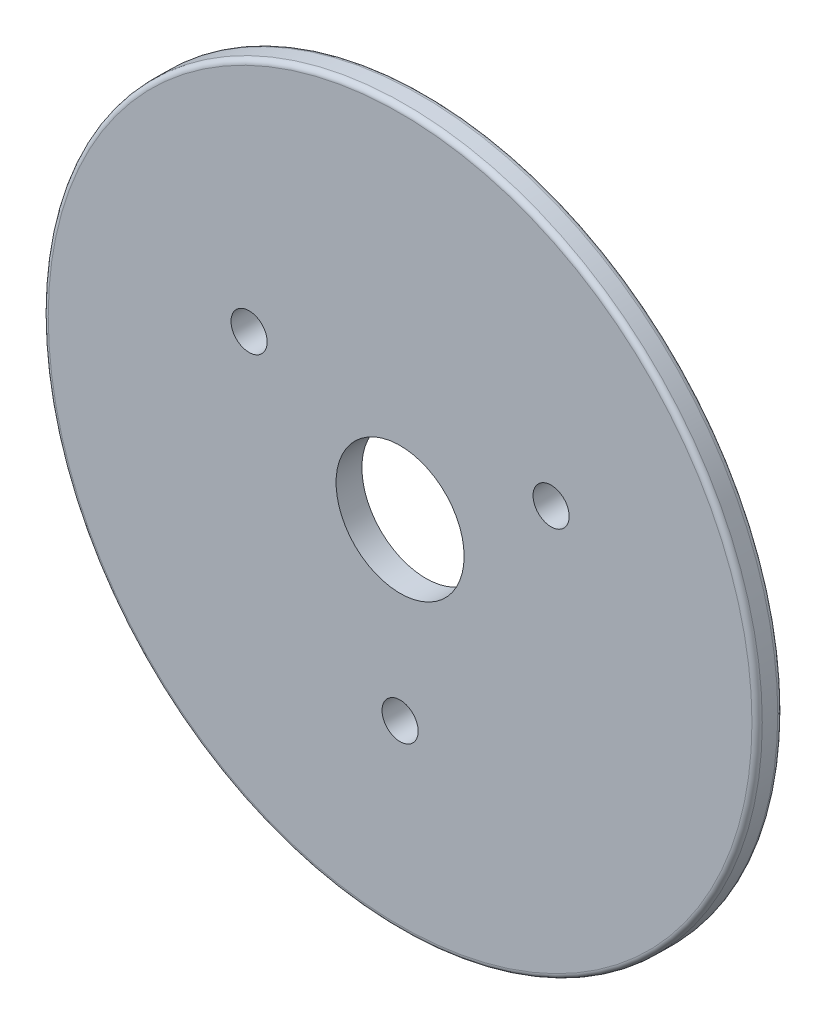
SolidWorks part; units mm, degrees
ref_plane "Front Plane" through (0, 0, 0) normal (0, 0, 1) x (1, 0, 0)
ref_plane "Top Plane" through (0, 0, 0) normal (0, 1, 0) x (1, 0, 0)
ref_plane "Right Plane" through (0, 0, 0) normal (1, 0, 0) x (0, 0, -1)
sketch "Sketch1" plane through (0, 0, 0) normal (0, 1, 0) x (1, 0, 0)
  line L0 (0, 36.1296) -> (0, -19.4741) construction
sketch "Sketch7" plane through (0, 0, 0) normal (0, 0, 1) x (1, 0, 0)
  line L0 (0, 0) -> (0, 28.5291) construction
  line L1 (-2.325, 29.4841) -> (-2.9401, 31.1741) construction
  line L2 (-2.325, 29.4841) -> (-1.6298, 27.5741) construction
  line L3 (-1.6298, 27.5741) -> (1.6298, 27.5741) construction
  line L4 (1.6298, 27.5741) -> (2.325, 29.4841) construction
  line L5 (2.325, 29.4841) -> (-2.325, 29.4841) construction
  line L6 (0, 27.5741) -> (0, 29.4841) construction
  line L7 (2.325, 29.4841) -> (2.9401, 31.1741) construction
  line L8 (-2.9401, 31.1741) -> (2.9401, 31.1741) construction
  line L9 (0, 0) -> (8.816, 27.1328) construction
  line L10 (8.816, 27.1328) -> (9.1394, 28.1281) construction
  line L11 (0, 29.4841) -> (0, 29.5757) construction
  line L12 (0, 29.5757) -> (0, 31.3125) construction
  line L13 (0, 30.4441) -> (9.4077, 28.954) construction
  line L14 (9.1394, 28.1281) -> (9.6761, 29.7799) construction
  circle A1 centre (0, 0) radius 28.5291 construction
  circle A2 centre (-1.2727, 28.0841) radius 0.51 construction
  circle A3 centre (1.2727, 28.0841) radius 0.51 construction
  circle A4 centre (0, 0) radius 29.5757
  circle A5 centre (0, 0) radius 31.3125 construction
  dimension "D3" = 40
  dimension "D6" = 1.02
  dimension "D1" = 3.6
  dimension "D2" = 18
  dimension "D7" = 9.525
  dimension "D4" = 1.91
  dimension "D5" = 4.65
extrude "Boss-Extrude1" add sketch "Sketch7" along normal blind 7.25 and the other way blind 7.25 contours A4 region at (0, 0, 0)
sketch "Sketch14" plane through (0, 0, 0) normal (1, 0, 0) x (0, 0, -1)
  line L0 (-18, 0) -> (-18, 10)
  line L1 (-18, 0) -> (0, 0)
  line L2 (0, 0) -> (0, 19)
  line L3 (0, 19) -> (-7.25, 19)
  line L4 (-7.25, 19) -> (-18, 10)
  line L5 (-7.25, 29.5757) -> (-7.25, -29.5757) construction
  line L6 (-18, 6.7395) -> (-3.3555, 19) construction
  arc A0 (-7.25, 19) -> (-18, 10) centre (-18.1316, 21.0773) cw
  dimension "D1" = 10
  dimension "D2" = 19
  dimension "D3" = 18
  dimension "D4" = 2.5
revolve "Revolve1" add sketch "Sketch14" angle 360 about L0 region at (0, 7.5733, 7.5341) region at (0, 9.2725, 16.1663) region at (0, 17.2765, 6.6188)
sketch "Sketch9" plane through (0, 0, 0) normal (0, 0, 1) x (1, 0, 0)
  line L0 (2, 0) -> (-2, 0) construction
  line L1 (-2, 0) -> (-2, 7.5) construction
  line L2 (-2, 7.5) -> (2, 7.5) construction
  line L3 (2, 7.5) -> (2, 0) construction
  circle A0 centre (0, 0) radius 6 construction
  dimension "D1" = 12
  dimension "D2" = 4
  dimension "D3" = 7.5
sketch "Sketch10" plane through (0, 0, 0) normal (0, 0, 1) x (1, 0, 0)
  line L0 (2, 0) -> (-2, 0) construction
  line L1 (-2.2, 7.7) -> (2.2, 7.7)
  line L2 (-2.2, 7.7) -> (-2.2, 0)
  line L3 (-2.2, 0) -> (2.2, 0)
  line L4 (2.2, 7.7) -> (2.2, 0)
  line L5 (-2, 7.5) -> (2, 7.5) construction
  line L6 (2, 7.5) -> (2, 0) construction
  circle A0 centre (0, 0) radius 6.2
  circle A1 centre (0, 0) radius 6 construction
  dimension "D1" = 0.2
  dimension "D2" = 0.2
  dimension "D3" = 0.2
extrude "Cut-Extrude3" cut sketch "Sketch10" against normal through all both and the other way through all contours A0 L4 L1 L2 | L2 A0 L4 L3 | L4 A0 L2 L3 region at (0, 6.8793, 0) region at (0, 3.0348, 0) region at (0, -0.8613, 0)
sketch "Sketch11" [suppressed] plane through (0, 0, 0) normal (0, 1, 0) x (1, 0, 0)
  line L0 (29.5757, 7.25) -> (-29.5757, 7.25) construction
  line L1 (11, 7.25) -> (17.5, 7.25)
  line L2 (11, 7.25) -> (11, 4.75)
  line L3 (11, 4.75) -> (17.5, 4.75)
  line L4 (17.5, 7.25) -> (17.5, 4.75)
  line L5 (-29.5757, -7.25) -> (29.5757, -7.25) construction
  line L6 (11, -7.25) -> (17.5, -7.25)
  line L7 (11, -7.25) -> (11, -4.75)
  line L8 (11, -4.75) -> (17.5, -4.75)
  line L9 (17.5, -7.25) -> (17.5, -4.75)
  line L11 (11, 4.75) -> (11, -4.75) construction
  line L12 (17.5, -4.75) -> (17.5, 4.75) construction
  line L13 (6.2, 7.25) -> (-6.2, 7.25) construction
  line L14 (0, 7.25) -> (22.5, 7.25)
  line L15 (0, 7.25) -> (0, -7.25)
  line L16 (0, -7.25) -> (22.5, -7.25)
  line L17 (22.5, 7.25) -> (22.5, -7.25)
  line L18 (-6.2, -7.25) -> (6.2, -7.25) construction
  line L19 (6, 7.25) -> (6, -7.25) construction
  dimension "D1" = 22.5
  dimension "D2" = 6
  dimension "D3" = 5
  dimension "D4" = 5
  dimension "D5" = 2.5
sketch "Sketch15" plane through (0, 0, -7.25) normal (0, 0, -1) x (-1, 0, 0)
  circle A0 centre (0, 0) radius 8.0081
  circle A1 centre (0, 0) radius 2.25
  dimension "D1" = 4.5
extrude "Boss-Extrude2" add sketch "Sketch15" against normal blind 5.5
sketch "Sketch16" plane through (0, 0, -7.25) normal (0, 0, -1) x (-1, 0, 0)
  circle A0 centre (0, 0) radius 5
  dimension "D1" = 10
extrude "Cut-Extrude4" cut sketch "Sketch16" against normal blind 3
sketch "Sketch17" plane through (0, 0, -7.25) normal (0, 0, -1) x (-1, 0, 0)
  circle A0 centre (0, 0) radius 29.5757
  circle A1 centre (0, 0) radius 29.5757 construction
  circle A2 centre (0, 0) radius 5
  circle A3 centre (0, 0) radius 5 construction
extrude "Boss-Extrude3" add sketch "Sketch17" along normal blind 7.5
sketch "Sketch8" plane through (0, 0, 0) normal (0, 0, 1) x (1, 0, 0)
  line L6 (-1.6298, 27.5741) -> (-2.3583, 29.5757)
  line L7 (-2.3583, 29.5757) -> (2.3583, 29.5757)
  line L8 (2.3583, 29.5757) -> (1.6298, 27.5741)
  line L9 (1.6298, 27.5741) -> (-1.6298, 27.5741)
  line L10 (-2.325, 29.4841) -> (-1.6298, 27.5741) construction
  line L11 (1.6298, 27.5741) -> (2.325, 29.4841) construction
  line L12 (6.9708, 26.7282) -> (6.8965, 28.8569)
  line L13 (6.8965, 28.8569) -> (11.3823, 27.3994)
  line L14 (11.3823, 27.3994) -> (10.0709, 25.7209)
  line L15 (10.0709, 25.7209) -> (6.9708, 26.7282)
  line L16 (14.8891, 23.2659) -> (15.4762, 25.3134)
  line L17 (15.4762, 25.3134) -> (19.292, 22.541)
  line L18 (19.292, 22.541) -> (17.5262, 21.35)
  line L19 (17.5262, 21.35) -> (14.8891, 23.2659)
  line L20 (21.35, 17.5262) -> (22.541, 19.292)
  line L21 (22.541, 19.292) -> (25.3134, 15.4762)
  line L22 (25.3134, 15.4762) -> (23.2659, 14.8891)
  line L23 (23.2659, 14.8891) -> (21.35, 17.5262)
  line L24 (25.7209, 10.0709) -> (27.3994, 11.3823)
  line L25 (27.3994, 11.3823) -> (28.8569, 6.8965)
  line L26 (28.8569, 6.8965) -> (26.7282, 6.9708)
  line L27 (26.7282, 6.9708) -> (25.7209, 10.0709)
  line L28 (27.5741, 1.6298) -> (29.5757, 2.3583)
  line L29 (29.5757, 2.3583) -> (29.5757, -2.3583)
  line L30 (29.5757, -2.3583) -> (27.5741, -1.6298)
  line L31 (27.5741, -1.6298) -> (27.5741, 1.6298)
  line L32 (26.7282, -6.9708) -> (28.8569, -6.8965)
  line L33 (28.8569, -6.8965) -> (27.3994, -11.3823)
  line L34 (27.3994, -11.3823) -> (25.7209, -10.0709)
  line L35 (25.7209, -10.0709) -> (26.7282, -6.9708)
  line L36 (23.2659, -14.8891) -> (25.3134, -15.4762)
  line L37 (25.3134, -15.4762) -> (22.541, -19.292)
  line L38 (22.541, -19.292) -> (21.35, -17.5262)
  line L39 (21.35, -17.5262) -> (23.2659, -14.8891)
  line L40 (17.5262, -21.35) -> (19.292, -22.541)
  line L41 (19.292, -22.541) -> (15.4762, -25.3134)
  line L42 (15.4762, -25.3134) -> (14.8891, -23.2659)
  line L43 (14.8891, -23.2659) -> (17.5262, -21.35)
  line L44 (10.0709, -25.7209) -> (11.3823, -27.3994)
  line L45 (11.3823, -27.3994) -> (6.8965, -28.8569)
  line L46 (6.8965, -28.8569) -> (6.9708, -26.7282)
  line L47 (6.9708, -26.7282) -> (10.0709, -25.7209)
  line L48 (1.6298, -27.5741) -> (2.3583, -29.5757)
  line L49 (2.3583, -29.5757) -> (-2.3583, -29.5757)
  line L50 (-2.3583, -29.5757) -> (-1.6298, -27.5741)
  line L51 (-1.6298, -27.5741) -> (1.6298, -27.5741)
  line L52 (-6.9708, -26.7282) -> (-6.8965, -28.8569)
  line L53 (-6.8965, -28.8569) -> (-11.3823, -27.3994)
  line L54 (-11.3823, -27.3994) -> (-10.0709, -25.7209)
  line L55 (-10.0709, -25.7209) -> (-6.9708, -26.7282)
  line L56 (-14.8891, -23.2659) -> (-15.4762, -25.3134)
  line L57 (-15.4762, -25.3134) -> (-19.292, -22.541)
  line L58 (-19.292, -22.541) -> (-17.5262, -21.35)
  line L59 (-17.5262, -21.35) -> (-14.8891, -23.2659)
  line L60 (-21.35, -17.5262) -> (-22.541, -19.292)
  line L61 (-22.541, -19.292) -> (-25.3134, -15.4762)
  line L62 (-25.3134, -15.4762) -> (-23.2659, -14.8891)
  line L63 (-23.2659, -14.8891) -> (-21.35, -17.5262)
  line L64 (-25.7209, -10.0709) -> (-27.3994, -11.3823)
  line L65 (-27.3994, -11.3823) -> (-28.8569, -6.8965)
  line L66 (-28.8569, -6.8965) -> (-26.7282, -6.9708)
  line L67 (-26.7282, -6.9708) -> (-25.7209, -10.0709)
  line L68 (-27.5741, -1.6298) -> (-29.5757, -2.3583)
  line L69 (-29.5757, -2.3583) -> (-29.5757, 2.3583)
  line L70 (-29.5757, 2.3583) -> (-27.5741, 1.6298)
  line L71 (-27.5741, 1.6298) -> (-27.5741, -1.6298)
  line L72 (-26.7282, 6.9708) -> (-28.8569, 6.8965)
  line L73 (-28.8569, 6.8965) -> (-27.3994, 11.3823)
  line L74 (-27.3994, 11.3823) -> (-25.7209, 10.0709)
  line L75 (-25.7209, 10.0709) -> (-26.7282, 6.9708)
  line L76 (-23.2659, 14.8891) -> (-25.3134, 15.4762)
  line L77 (-25.3134, 15.4762) -> (-22.541, 19.292)
  line L78 (-22.541, 19.292) -> (-21.35, 17.5262)
  line L79 (-21.35, 17.5262) -> (-23.2659, 14.8891)
  line L80 (-17.5262, 21.35) -> (-19.292, 22.541)
  line L81 (-19.292, 22.541) -> (-15.4762, 25.3134)
  line L82 (-15.4762, 25.3134) -> (-14.8891, 23.2659)
  line L83 (-14.8891, 23.2659) -> (-17.5262, 21.35)
  line L84 (-10.0709, 25.7209) -> (-11.3823, 27.3994)
  line L85 (-11.3823, 27.3994) -> (-6.8965, 28.8569)
  line L86 (-6.8965, 28.8569) -> (-6.9708, 26.7282)
  line L87 (-6.9708, 26.7282) -> (-10.0709, 25.7209)
  circle A0 centre (0, 0) radius 29.5757 construction
  point P119 (0, 0)
  dimension "D1" = 20
extrude "Cut-Extrude2" cut sketch "Sketch8" against normal through all both and the other way through all
fillet "Fillet2" radius 0.51 80 edges at (-28.7595, -6.8999, -3.75) (-27.3226, -11.3223, -3.75) (-25.2198, -15.4494, -3.75) (-22.4866, -19.2113, -3.75) (-19.2113, -22.4866, -3.75) (-15.4494, -25.2198, -3.75) (-11.3223, -27.3226, -3.75) (-6.8999, -28.7595, -3.75) (-2.325, -29.4841, -3.75) (2.325, -29.4841, -3.75) (6.8999, -28.7595, -3.75) (11.3223, -27.3226, -3.75) (15.4494, -25.2198, -3.75) (19.2113, -22.4866, -3.75) (22.4866, -19.2113, -3.75) (25.2198, -15.4494, -3.75) (27.3226, -11.3223, -3.75) (28.7595, -6.8999, -3.75) (29.4841, -2.325, -3.75) (29.4841, 2.325, -3.75) (28.7595, 6.8999, -3.75) (27.3226, 11.3223, -3.75) (25.2198, 15.4494, -3.75) (22.4866, 19.2113, -3.75) (19.2113, 22.4866, -3.75) (15.4494, 25.2198, -3.75) (11.3223, 27.3226, -3.75) (6.8999, 28.7595, -3.75) (2.325, 29.4841, -3.75) (-26.7282, -6.9708, -3.75) (-25.7209, -10.0709, -3.75) (-23.2659, -14.8891, -3.75) (-21.35, -17.5262, -3.75) (-17.5262, -21.35, -3.75) (-14.8891, -23.2659, -3.75) (-10.0709, -25.7209, -3.75) (-6.9708, -26.7282, -3.75) (-1.6298, -27.5741, -3.75) (1.6298, -27.5741, -3.75) (6.9708, -26.7282, -3.75) (10.0709, -25.7209, -3.75) (14.8891, -23.2659, -3.75) (17.5262, -21.35, -3.75) (21.35, -17.5262, -3.75) (23.2659, -14.8891, -3.75) (25.7209, -10.0709, -3.75) (26.7282, -6.9708, -3.75) (27.5741, -1.6298, -3.75) (27.5741, 1.6298, -3.75) (26.7282, 6.9708, -3.75) (25.7209, 10.0709, -3.75) (23.2659, 14.8891, -3.75) (21.35, 17.5262, -3.75) (17.5262, 21.35, -3.75) (14.8891, 23.2659, -3.75) (10.0709, 25.7209, -3.75) (6.9708, 26.7282, -3.75) (1.6298, 27.5741, -3.75) (-1.6298, 27.5741, -3.75) (-2.325, 29.4841, -3.75) (-6.8999, 28.7595, -3.75) (-6.9708, 26.7282, -3.75) (-10.0709, 25.7209, -3.75) (-11.3223, 27.3226, -3.75) (-15.4494, 25.2198, -3.75) (-14.8891, 23.2659, -3.75) (-17.5262, 21.35, -3.75) (-19.2113, 22.4866, -3.75) (-22.4866, 19.2113, -3.75) (-21.35, 17.5262, -3.75) (-23.2659, 14.8891, -3.75) (-25.2198, 15.4494, -3.75) (-27.3226, 11.3223, -3.75) (-25.7209, 10.0709, -3.75) (-26.7282, 6.9708, -3.75) (-28.7595, 6.8999, -3.75) (-29.4841, 2.325, -3.75) (-27.5741, 1.6298, -3.75) (-27.5741, -1.6298, -3.75) (-29.4841, -2.325, -3.75)
sketch "Sketch18" plane through (0, 0, -14.75) normal (0, 0, -1) x (-1, 0, 0)
  circle A0 centre (0, 0) radius 5
  circle A1 centre (0, 0) radius 34.5757
  circle A2 centre (0, 0) radius 29.5757
  circle A3 centre (0, 0) radius 5 construction
  circle A4 centre (0, 0) radius 29.5757 construction
  dimension "D1" = 5
extrude "Boss-Extrude4" add sketch "Sketch18" along normal blind 2.5 contours A1 A2 | A2 A0 region at (33.5977, 0, -14.75) region at (28.7391, 0, -14.75)
sketch "Sketch19" plane through (0, 0, 7.25) normal (0, 0, 1) x (1, 0, 0)
  circle A0 centre (0, 0) radius 19
  circle A1 centre (0, 0) radius 34.5757
  circle A2 centre (0, 0) radius 34.5757 construction
  circle A3 centre (0, 0) radius 19 construction
extrude "Boss-Extrude5" add sketch "Sketch19" against normal blind 2.5
sketch "Sketch20" plane through (0, 0, 18) normal (0, 0, 1) x (1, 0, 0)
  line L0 (-2.2, 5.7966) -> (-2.2, 7.7)
  line L1 (-2.2, 7.7) -> (2.2, 7.7)
  line L2 (-2.2, 7.7) -> (2.2, 7.7) construction
  line L3 (2.2, 7.7) -> (2.2, 5.7966)
  circle A0 centre (0, 0) radius 6.2
  arc A1 (-2.2, 5.7966) -> (2.2, 5.7966) centre (0, 0) ccw construction
  arc M2 (2.2, 5.7966) -> (-2.2, 5.7966) centre (0, 0) cw
  line M3 (-2.2, 5.7966) -> (-2.2, 7.7)
  line M4 (-2.2, 7.7) -> (2.2, 7.7)
  line M5 (2.2, 7.7) -> (2.2, 5.7966)
extrude "Cut-Extrude5" cut sketch "Sketch20" against normal through all contours A0 M5 M4 M3 | A0 M2 region at (0, 6.8793, 18) region at (0, 0, 18)
fillet "Fillet3" radius 0.5 12 edges at (2.2, 5.7966, 0.375) (-2.2, 5.7966, 0.375) (2.2, 6.7483, 18) (-2.2, 6.7483, 18) (0, 7.7, 18) (-19, 0, 7.25) (-10, 0, 18) (0, -6.2, 18) (34.5757, 0, 4.75) (-34.5757, 0, -14.75) (-34.5757, 0, -17.25) (34.5757, 0, 7.25)
ref_plane "Plane1" through (0, 0, -5.25) normal (0, 0, 1) x (1, 0, 0)
sketch "Sketch21" plane through (0, 0, -5.25) normal (0, 0, 1) x (1, 0, 0)
  circle A0 centre (0, 0) radius 8.0081
  circle A1 centre (0, 0) radius 2.25
  circle A2 centre (0, 0) radius 6.2
  arc A3 (-2.4985, 5.6743) -> (2.4985, 5.6743) centre (0, 0) ccw construction
  dimension "D1" = 4.5
extrude "Boss-Extrude6" add sketch "Sketch21" against normal blind 2.5 contours A2 A1 | A0 A2 region at (-7.7816, 0, -5.25) region at (-6.0246, 0, -5.25)
extrude "Boss-Extrude7" add sketch "Sketch21<4>" against normal up to surface (12 mm away) contours A0 A2 region at (-7.7816, 0, -5.25) up to face at (-34.0757, 0, -17.25)
sketch "Sketch21<4>" plane through (0, 0, -5.25) normal (0, 0, 1) x (1, 0, 0) same geometry as "Sketch21"
sketch "Sketch23" plane through (0, 0, -14.75) normal (0, 0, 1) x (1, 0, 0)
  line L0 (0, 27.5741) -> (0, 6.2) construction
  line L2 (1.2727, 27.5741) -> (-1.2727, 27.5741) construction
  circle A0 centre (0, 0) radius 16.8871 construction
  circle A1 centre (0, 0) radius 6.2 construction
  circle A2 centre (0, -16.8871) radius 1.75
  circle A3 centre (-14.6246, 8.4435) radius 1.75
  circle A4 centre (14.6246, 8.4435) radius 1.75
  point P10 (0, 16.8871)
  point P19 (0, 0)
  point P26 (0, 0)
  dimension "D1" = 3.5
  dimension "D2" = 3
extrude "Cut-Extrude7" cut sketch "Sketch23" along normal blind 10 and the other way through all
ref_plane "Plane2" through (0, 0, -12.25) normal (0, 0, 1) x (1, 0, 0)
sketch "Sketch24" plane through (0, 0, -12.25) normal (0, 0, 1) x (1, 0, 0)
  line L0 (0, -16.8871) -> (0, 0) construction
  line L1 (-14.6246, 5.0949) -> (-11.7246, 6.7692)
  line L2 (-11.7246, 6.7692) -> (-11.7246, 10.1178)
  line L3 (-11.7246, 10.1178) -> (-14.6246, 11.7922)
  line L4 (-14.6246, 11.7922) -> (-17.5246, 10.1178)
  line L5 (-17.5246, 10.1178) -> (-17.5246, 6.7692)
  line L6 (-17.5246, 6.7692) -> (-14.6246, 5.0949)
  line L7 (2.9, -18.5614) -> (2.9, -15.2127)
  line L8 (2.9, -15.2127) -> (0, -13.5384)
  line L9 (0, -13.5384) -> (-2.9, -15.2127)
  line L10 (-2.9, -15.2127) -> (-2.9, -18.5614)
  line L11 (-2.9, -18.5614) -> (0, -20.2357)
  line L12 (0, -20.2357) -> (2.9, -18.5614)
  line L13 (14.6246, 5.0949) -> (17.5246, 6.7692)
  line L14 (17.5246, 6.7692) -> (17.5246, 10.1178)
  line L15 (17.5246, 10.1178) -> (14.6246, 11.7922)
  line L16 (14.6246, 11.7922) -> (11.7246, 10.1178)
  line L17 (11.7246, 10.1178) -> (11.7246, 6.7692)
  line L18 (11.7246, 6.7692) -> (14.6246, 5.0949)
  line L19 (0, 0) -> (14.6246, 8.4435) construction
  line L21 (-14.6246, 8.4435) -> (0, 0) construction
  circle A0 centre (-14.6246, 8.4435) radius 2.9 construction
  circle A1 centre (0, -16.8871) radius 2.9 construction
  circle A2 centre (14.6246, 8.4435) radius 2.9 construction
  dimension "D1" = 5.8
extrude "Cut-Extrude8" cut sketch "Sketch24" along normal blind 3 contours L13 L14 L15 L16 | L13 L16 L17 L18 | L3 L4 L5 L6 | L3 L6 L1 L2 | L10 L7 L8 L9 | L10 L11 L12 L7 region at (-14.6246, 8.4435, -12.25) region at (0, -16.8871, -12.25) region at (14.6246, 8.4435, -12.25)
sketch "Sketch25" plane through (0, 0, -9.25) normal (0, 0, -1) x (-1, 0, 0)
  circle A0 centre (0, -16.8871) radius 1.75
  circle A1 centre (14.6246, 8.4435) radius 1.75
  circle A2 centre (-14.6246, 8.4435) radius 1.75
  circle A3 centre (0, -16.8871) radius 1.75 construction
extrude "Boss-Extrude8" add sketch "Sketch25" against normal blind 0.2
sketch "Sketch22" plane through (0, 0, 0) normal (0, 1, 0) x (1, 0, 0)
  line L0 (34.5757, 15.25) -> (34.5757, 16.75) construction
  line L1 (-34.5757, 17.25) -> (34.5757, 17.25)
  line L2 (-34.5757, 17.25) -> (-34.5757, 14.75)
  line L3 (-34.5757, 14.75) -> (34.5757, 14.75)
  line L4 (34.5757, 17.25) -> (34.5757, 14.75)
  line L5 (-34.5757, 17.25) -> (34.5757, 14.75) construction
  line L6 (-34.5757, 14.75) -> (34.5757, 17.25) construction
  line L7 (-32.1547, -18) -> (32.1547, -18) construction
  line L8 (-34.5757, 14.75) -> (34.5757, 14.75)
  line L9 (-34.5757, 14.75) -> (-34.5757, -18)
  line L10 (-34.5757, -18) -> (34.5757, -18)
  line L11 (34.5757, 14.75) -> (34.5757, -18)
  line L12 (-34.0757, 14.75) -> (34.0757, 14.75) construction
  line L13 (1.75, 17.25) -> (-1.75, 17.25) construction
  line L14 (-34.5757, 16.75) -> (-34.5757, 15.25) construction
  point P0 (0, 16)
extrude "Cut-Extrude10" cut sketch "Sketch22" against normal through all both and the other way through all contours L11 L3 L9 L10 region at (0, 0, 1.625)
